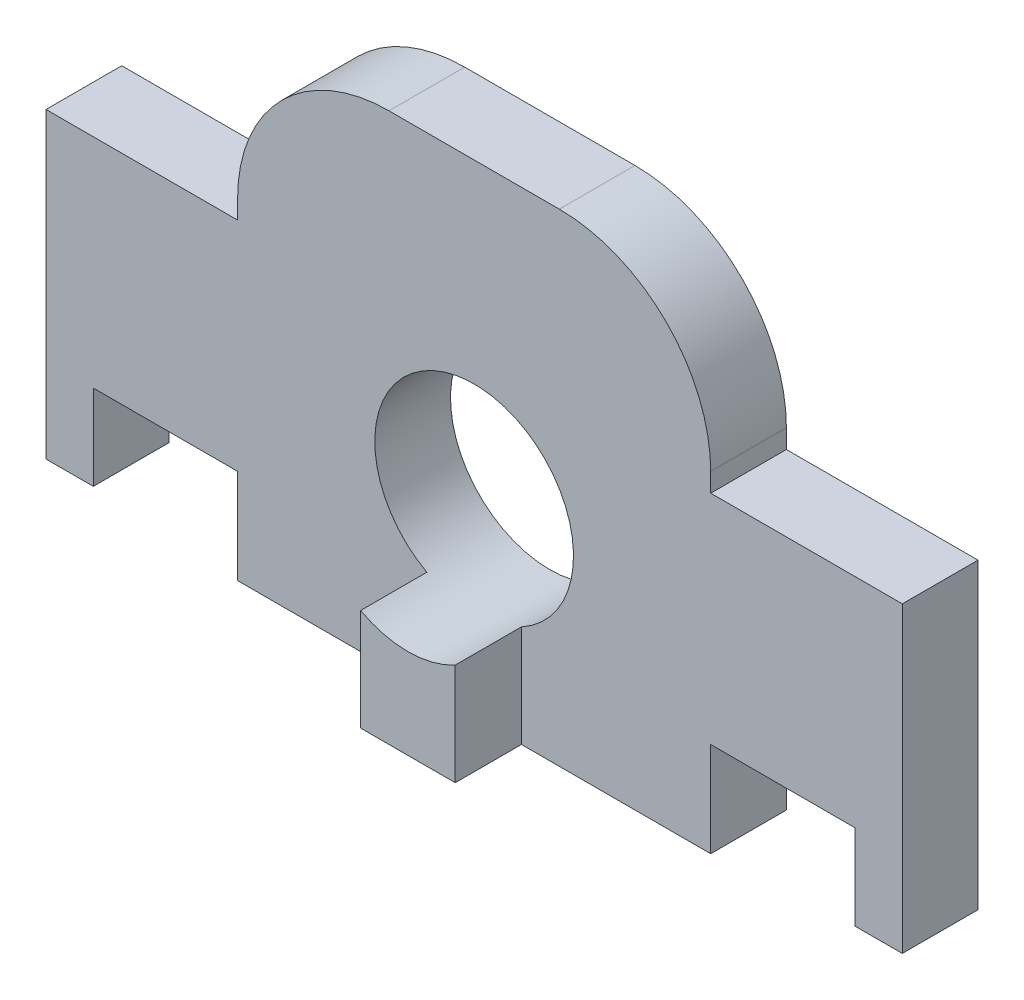
SolidWorks part; units mm, degrees
ref_plane "Front Plane" through (0, 0, 0) normal (0, 0, 1) x (1, 0, 0)
ref_plane "Top Plane" through (0, 0, 0) normal (0, 1, 0) x (1, 0, 0)
ref_plane "Right Plane" through (0, 0, 0) normal (1, 0, 0) x (0, 0, -1)
sketch "Sketch2" plane through (0, 0, 0) normal (0, 0, 1) x (1, 0, 0)
  line L0 (1.0743, 13.7948) -> (1.0743, -6.7052) construction
  line L1 (-33.9257, 13.7948) -> (36.0743, 13.7948)
  line L2 (-33.9257, 13.7948) -> (-33.9257, -37.2052)
  line L3 (-33.9257, -37.2052) -> (36.0743, -37.2052)
  line L4 (36.0743, 13.7948) -> (36.0743, -37.2052)
  line L5 (1.0743, -27.7052) -> (1.0743, -37.2052)
  line L6 (1.0743, -27.7052) -> (1.0743, -37.2052) construction
  circle A0 centre (1.0743, -17.2052) radius 10.5
  dimension "D1" = 70
  dimension "D2" = 51
  dimension "D3" = 20
extrude "Boss-Extrude1" add sketch "Sketch2" along normal blind 15 contours A0 L3 L4 L1 L2 region at (1.0743, 12.9287, 0)
sketch "Sketch3" plane through (0, 0, 15) normal (0, 0, 1) x (1, 0, 0)
  line L12 (26.0743, -37.2052) -> (36.0743, -37.2052)
  line L13 (-33.9257, -37.2052) -> (-23.9257, -37.2052)
  line L14 (-33.9257, -37.2052) -> (-33.9257, -27.2052)
  line L15 (-33.9257, -27.2052) -> (-23.9257, -27.2052)
  line L16 (-23.9257, -37.2052) -> (-23.9257, -27.2052)
  line L17 (26.0743, -37.2052) -> (26.0743, -27.2052)
  line L18 (26.0743, -27.2052) -> (36.0743, -27.2052)
  line L19 (36.0743, -37.2052) -> (36.0743, -27.2052)
  line L20 (-33.9257, 13.7948) -> (-23.9257, 13.7948)
  line L21 (-33.9257, 13.7948) -> (-33.9257, -4.2052)
  line L22 (-33.9257, -4.2052) -> (-23.9257, -4.2052)
  line L23 (-23.9257, -2.2052) -> (-23.9257, -4.2052)
  line L24 (36.0743, 13.7948) -> (26.0743, 13.7948)
  line L25 (36.0743, 13.7948) -> (36.0743, -4.2052)
  line L26 (36.0743, -4.2052) -> (26.0743, -4.2052)
  line L27 (26.0743, -2.2052) -> (26.0743, -4.2052)
  line L28 (-7.9257, 13.7948) -> (10.0743, 13.7948)
  arc A6 (-7.9257, 13.7948) -> (-23.9257, -2.2052) centre (-7.9257, -2.2052) ccw
  arc A7 (10.0743, 13.7948) -> (26.0743, -2.2052) centre (10.0743, -2.2052) cw
  line M5 (-33.9257, 13.7948) -> (-33.9257, -37.2052)
  line M7 (36.0743, -37.2052) -> (36.0743, 13.7948)
  line M8 (36.0743, 13.7948) -> (-33.9257, 13.7948)
  dimension "D5" = 10
  dimension "D6" = 16
  dimension "D11" = 16
  dimension "D2" = 10
  dimension "D3" = 18
  dimension "D4" = 18
  dimension "D7" = 10
  dimension "D8" = 10
  dimension "D9" = 10
  dimension "D10" = 10
extrude "Cut-Extrude1" cut sketch "Sketch3" against normal through all contours M8 M5 | M7 M8 | L14 L13 L16 L15 | L12 L19 L18 L17 region at (-26.9208, 6.0637, 15) region at (29.0694, 6.0637, 15)
sketch "Sketch4" plane through (0, 0, 15) normal (0, 0, 1) x (1, 0, 0)
  line L0 (-3.9257, -26.4383) -> (-3.9257, -37.2052)
  line L1 (-23.9257, -37.2052) -> (26.0743, -37.2052) construction
  line L2 (-3.9257, -37.2052) -> (-23.9257, -37.2052)
  line L3 (-23.9257, -37.2052) -> (-23.9257, -27.2052)
  line L4 (-23.9257, -27.2052) -> (-33.9257, -27.2052)
  line L5 (-33.9257, -27.2052) -> (-33.9257, -4.2052)
  line L6 (-33.9257, -4.2052) -> (-23.9257, -4.2052)
  line L7 (-23.9257, -4.2052) -> (-23.9257, 13.7948)
  line L8 (-23.9257, 13.7948) -> (26.0743, 13.7948)
  line L9 (26.0743, 13.7948) -> (26.0743, -4.2052)
  line L10 (26.0743, -4.2052) -> (36.0743, -4.2052)
  line L11 (36.0743, -4.2052) -> (36.0743, -27.2052)
  line L12 (36.0743, -27.2052) -> (26.0743, -27.2052)
  line L13 (26.0743, -27.2052) -> (26.0743, -37.2052)
  line L14 (26.0743, -37.2052) -> (6.0743, -37.2052)
  line L15 (6.0743, -37.2052) -> (6.0743, -26.4383)
  line L16 (1.0743, 13.7948) -> (1.0743, -37.2052) construction
  line L17 (-33.9257, -15.7052) -> (36.0743, -15.7052) construction
  line L18 (-9.4257, -17.2052) -> (11.5743, -17.2052) construction
  line L19 (1.0743, -37.2052) -> (-3.9257, -37.2052)
  line L20 (1.0743, -37.2052) -> (6.0743, -37.2052)
  line L21 (-3.9257, -26.4383) -> (6.0743, -26.4383)
  circle A0 centre (1.0743, -17.2052) radius 10.5 construction
  circle M6 centre (1.0743, -17.2052) radius 10.5
  line M7 (36.0743, -27.2052) -> (36.0743, -4.2052)
  line M8 (36.0743, -4.2052) -> (26.0743, -4.2052)
  line M9 (26.0743, -4.2052) -> (26.0743, -2.2052)
  arc M10 (26.0743, -2.2052) -> (10.0743, 13.7948) centre (10.0743, -2.2052) ccw
  line M11 (10.0743, 13.7948) -> (-7.9257, 13.7948)
  arc M12 (-7.9257, 13.7948) -> (-23.9257, -2.2052) centre (-7.9257, -2.2052) ccw
  line M13 (-23.9257, -2.2052) -> (-23.9257, -4.2052)
  line M14 (-23.9257, -4.2052) -> (-33.9257, -4.2052)
  line M15 (-33.9257, -4.2052) -> (-33.9257, -27.2052)
  line M16 (-33.9257, -27.2052) -> (-23.9257, -27.2052)
  line M17 (-23.9257, -27.2052) -> (-23.9257, -37.2052)
  line M18 (-23.9257, -37.2052) -> (26.0743, -37.2052)
  line M19 (26.0743, -37.2052) -> (26.0743, -27.2052)
  line M20 (26.0743, -27.2052) -> (36.0743, -27.2052)
  dimension "D1" = 5
  dimension "D2" = 5
extrude "Cut-Extrude2" cut sketch "Sketch4" against normal blind 7 contours L15 L0 M18 M19 M20 M7 M8 M9 M10 M11 M12 M13 M14 M15 M16 M17 M6 region at (-4.7918, -31.8217, 15)
sketch "Sketch5" plane through (0, -4.2052, 0) normal (0, 1, 0) x (1, 0, 0)
  line L1 (-33.9257, 0) -> (-39.1757, 0)
  line L2 (-33.9257, 0) -> (-33.9257, -8)
  line L3 (-33.9257, -8) -> (-39.1757, -8)
  line L4 (-39.1757, 0) -> (-39.1757, -8)
  line L6 (-39.1757, 0) -> (-44.1757, 0)
  line L7 (-39.1757, 0) -> (-39.1757, -8)
  line L8 (-39.1757, -8) -> (-44.1757, -8)
  line L9 (-44.1757, 0) -> (-44.1757, -8)
  line L10 (36.0743, 0) -> (41.3243, 0)
  line L11 (36.0743, 0) -> (36.0743, -8)
  line L12 (36.0743, -8) -> (41.3243, -8)
  line L13 (41.3243, 0) -> (41.3243, -8)
  line L14 (41.3243, -8) -> (46.3243, -8)
  line L15 (41.3243, -8) -> (41.3243, 0)
  line L16 (41.3243, 0) -> (46.3243, 0)
  line L17 (46.3243, -8) -> (46.3243, 0)
  line M10 (-33.9257, 0) -> (-33.9257, -8)
  dimension "D1" = 8
  dimension "D2" = 5.25
  dimension "D3" = 8
  dimension "D4" = 5
  dimension "D5" = 8
  dimension "D6" = 5.25
  dimension "D7" = 5
extrude "Boss-Extrude2" add sketch "Sketch5" against normal blind 23 contours L1 L4 L3 M10 region at (-36.5507, -4.2052, 4)
extrude "Boss-Extrude3" add sketch "Sketch5<3>" against normal blind 32 contours L6 L9 L8 L4 region at (-41.6757, -4.2052, 4)
sketch "Sketch5<3>" plane through (0, -4.2052, 0) normal (0, 1, 0) x (1, 0, 0) same geometry as "Sketch5"
extrude "Boss-Extrude4" add sketch "Sketch5<5>" against normal blind 32 separate body contours L14 L17 L16 L13 region at (43.8243, -4.2052, 4)
sketch "Sketch5<5>" plane through (0, -4.2052, 0) normal (0, 1, 0) x (1, 0, 0) same geometry as "Sketch5"
extrude "Boss-Extrude5" add sketch "Sketch5<6>" against normal blind 23 contours L13 L10 L11 L12 region at (38.6993, -4.2052, 4)
sketch "Sketch5<6>" plane through (0, -4.2052, 0) normal (0, 1, 0) x (1, 0, 0) same geometry as "Sketch5"
